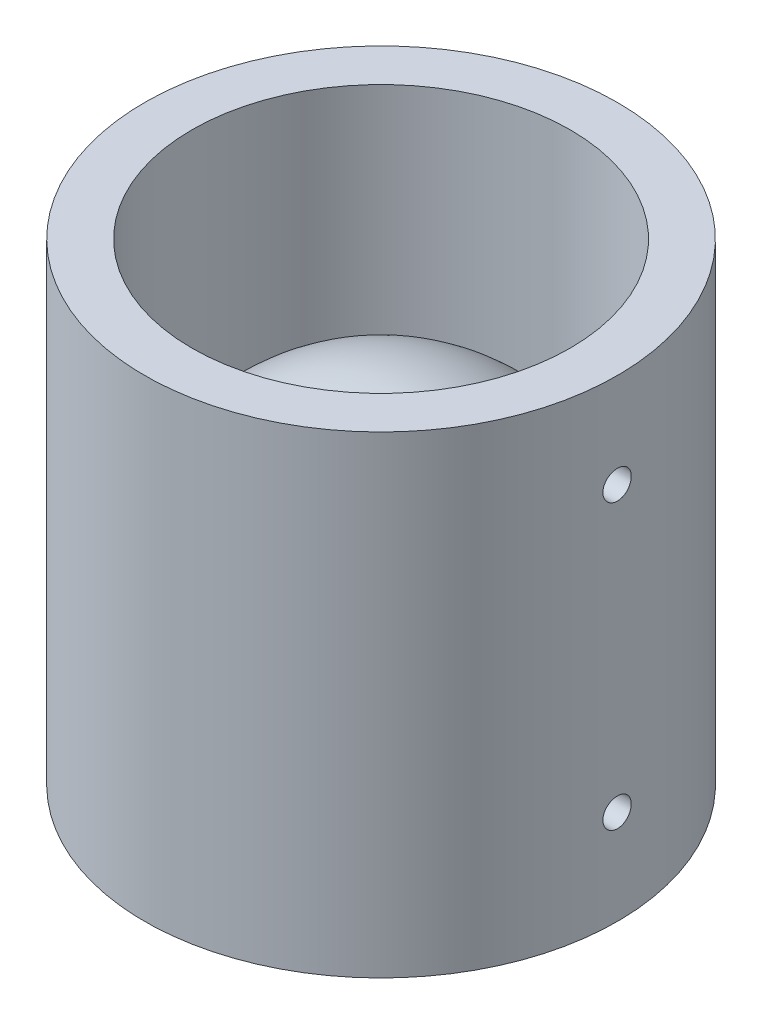
SolidWorks part; units mm, degrees
ref_plane "Front Plane" through (0, 0, 0) normal (0, 0, 1) x (1, 0, 0)
ref_plane "Top Plane" through (0, 0, 0) normal (0, 1, 0) x (1, 0, 0)
ref_plane "Right Plane" through (0, 0, 0) normal (1, 0, 0) x (0, 0, -1)
sketch "Sketch1" plane through (0, 0, 0) normal (0, 0, 1) x (1, 0, 0)
  line L0 (0, 0) -> (0, 24.8092) construction
  line L1 (7.99, 8.5) -> (6.3213, 14.7276) construction
  line L2 (10, 0) -> (8, 0)
  line L3 (10, 0) -> (10, 20)
  line L4 (10, 20) -> (8, 20)
  line L5 (8, 0) -> (8, 20)
  line L6 (8, 8.5) -> (7.99, 8.5)
  line L7 (8, 8.5) -> (8, 4.5)
  line L8 (8, 4.5) -> (7.99, 4.5)
  line L9 (7.99, 8.5) -> (7.99, 4.5)
  line L10 (7.99, 4.5) -> (7.39, 4.5)
  line L11 (0, 14.6309) -> (0, 13.2309)
  line L12 (7.39, 4.5) -> (8.4415, 10.7771) construction
  arc A0 (0, 14.6309) -> (7.99, 8.5) centre (0, 6.3591) cw
  arc A1 (0, 13.2309) -> (7.39, 4.5) centre (0, 5.738) cw
  dimension "D1" = 8
  dimension "D2" = 2
  dimension "D3" = 20
  dimension "D4" = 4
  dimension "D5" = 0.01
  dimension "D6" = 1.4
  dimension "D7" = 75
  dimension "D8" = 0.6
  dimension "D9" = 4.5
  dimension "D10" = 5.3691
  dimension "D11" = 6.1309
revolve "Revolve1" add sketch "Sketch1" angle 360 about L0
ref_plane "Plane1" through (10, 0, 0) normal (1, 0, 0) x (0, 0, -1)
sketch "Sketch2" plane through (10, 0, 0) normal (1, 0, 0) x (0, 0, -1)
  line L0 (0, 0) -> (0, 20) construction
  line L1 (0, 0) -> (0, 20)
  line L2 (8, 20) -> (-8, 20) construction
  line L4 (-0.6, 16) -> (0.6, 16)
  line L5 (-0.6, 16) -> (-0.25, 16.6)
  line L6 (-0.25, 16.6) -> (0.25, 16.6)
  line L7 (0.6, 16) -> (0.25, 16.6)
  line L8 (-0.6, 4) -> (0.6, 4)
  line L9 (-0.6, 4) -> (-0.25, 4.6)
  line L10 (-0.25, 4.6) -> (0.25, 4.6)
  line L11 (0.6, 4) -> (0.25, 4.6)
  circle A0 centre (0, 16) radius 0.6
  circle A1 centre (0, 4) radius 0.6
  point P12 (0.6, 16.6)
  point P17 (0.4192, 16.6)
  point P18 (0.2867, 16.6)
  point P19 (-0.3095, 16.6)
  point P20 (0, 0)
  point P21 (0, 16.6)
  point P22 (0, 4.6)
  dimension "D3" = 1.2
  dimension "D1" = 4
  dimension "D2" = 4
  dimension "D4" = 0.5
  dimension "D5" = 0.5
extrude "Cut-Extrude1" cut sketch "Sketch2" against normal up to next contours L1 A0 | L1 A0 | L1 A1 | L1 A1 | L4 A0 L1 | L1 A0 L4 | L1 A1 L8 | L8 A1 L1 | L7 A0 | L5 A0 | L11 A1 | L9 A1
chamfer "Chamfer1" distance 0.5 distance2 1 1 edges at (-7.39, 4.5, 0)
